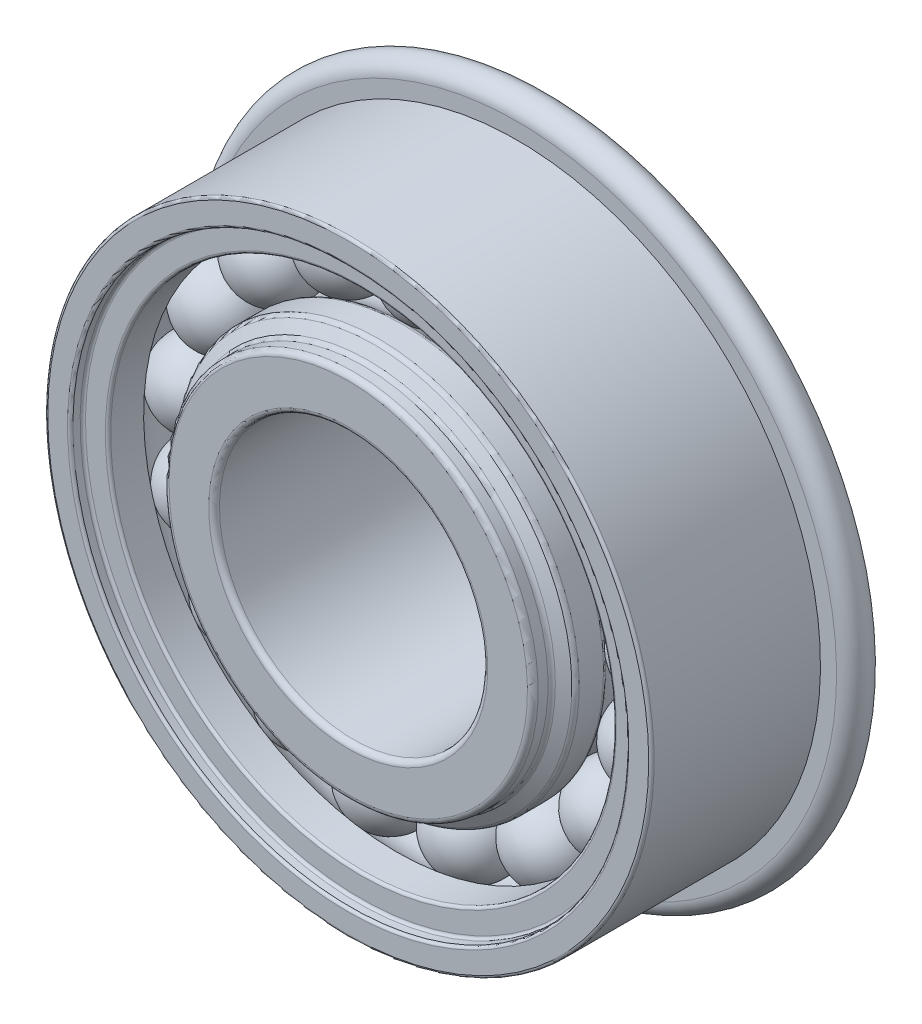
SolidWorks part; units mm, degrees
ref_plane "Front Plane" through (0, 0, 0) normal (0, 0, 1) x (1, 0, 0)
ref_plane "Top Plane" through (0, 0, 0) normal (0, 1, 0) x (1, 0, 0)
ref_plane "Right Plane" through (0, 0, 0) normal (1, 0, 0) x (0, 0, -1)
sketch "Sketch1" plane through (0, 0, 0) normal (1, 0, 0) x (0, 0, -1)
  line L0 (-5.5562, 0) -> (5.5562, 0) construction
  line L1 (3.9688, 0) -> (3.9688, 15.875)
  line L2 (3.9688, 15.875) -> (2.4448, 15.875)
  line L3 (2.4448, 15.875) -> (2.4447, 14.351)
  line L4 (2.4447, 14.351) -> (-5.5562, 14.351)
  line L5 (-5.5562, 6.35) -> (3.9688, 6.35)
  line L6 (-5.5562, 8.7376) -> (5.5563, 8.7376)
  line L7 (-1.5557, 14.351) -> (-1.5557, 10.3822) construction
  arc A0 (2.4448, 15.113) -> (3.9688, 15.113) centre (3.2068, 15.113) cw
  point P4 (0, 0)
  dimension "Inner Ring Width" = 11.1125
  dimension "Flange OD" = 31.75
  dimension "OD" = 28.702
  dimension "Width" = 9.525
  dimension "ID" = 12.7
  dimension "Inner Ring OD" = 17.4752
  dimension "Flange Thickness" = 1.524
  dimension "Ball Diameter" = 3.9688
  dimension "For Shaft Diameter" = 12.7
  dimension "For Housing ID" = 28.702
sketch "Sketch2" plane through (0, 0, 0) normal (1, 0, 0) x (0, 0, -1)
  line L0 (2.4447, 14.351) -> (-5.5562, 14.351) construction
  line L1 (2.4447, 14.351) -> (-5.5562, 14.351)
  line L2 (2.4447, 14.351) -> (2.4448, 15.113)
  line L3 (3.9688, 15.113) -> (3.9688, 11.9682)
  line L4 (3.9688, 0) -> (3.9688, 15.875) construction
  line L5 (3.9688, 11.9682) -> (0.1628, 11.9682)
  line L6 (-4.9605, 11.9682) -> (-4.9605, 13.1596)
  line L7 (-4.9605, 13.1596) -> (-5.5562, 13.1596)
  line L8 (-5.5562, 13.1596) -> (-5.5562, 14.351)
  line L9 (-1.5557, 12.9604) -> (-1.5557, 14.351) construction
  line L10 (-1.5557, 6.35) -> (-1.5557, 7.5438) construction
  line L11 (-1.5557, 7.5438) -> (-1.5557, 8.7376) construction
  line L12 (-5.5562, 8.7376) -> (5.5563, 8.7376) construction
  line L13 (-5.5562, 6.35) -> (3.9688, 6.35) construction
  line L14 (-1.5557, 12.9604) -> (-1.5557, 11.9682) construction
  line L15 (-1.5557, 11.9682) -> (-1.5557, 10.976) construction
  line L16 (-3.2743, 11.9682) -> (-4.9605, 11.9682)
  line L17 (-4.3648, 13.1596) -> (-5.5562, 13.1596) construction
  arc A0 (3.9688, 15.113) -> (2.4448, 15.113) centre (3.2068, 15.113) ccw construction
  arc A1 (3.9688, 15.113) -> (2.4448, 15.113) centre (3.2068, 15.113) ccw
  circle A2 centre (-1.5557, 10.976) radius 1.9844 construction
  arc A3 (-3.2743, 11.9682) -> (0.1628, 11.9682) centre (-1.5557, 10.976) cw
  point P10 (-1.5557, 14.351)
  point P12 (-1.5557, 8.9916)
  point P23 (-1.5557, 8.7376)
  point P24 (-1.5557, 11.9682)
  point P33 (-4.9605, 13.1596)
  dimension "D1" = 3.9688
  dimension "D2" = 0.254
revolve "Revolve1" add sketch "Sketch2" angle 360 about L0
sketch "Sketch3" plane through (0, 0, 0) normal (1, 0, 0) x (0, 0, -1)
  line L0 (-5.5562, 8.7376) -> (5.5563, 8.7376) construction
  line L1 (-5.5562, 8.7376) -> (-4.6901, 8.7376)
  line L2 (5.5563, 8.7376) -> (5.5563, 6.35)
  line L3 (5.5563, 6.35) -> (-5.5562, 6.35)
  line L4 (-5.5562, 6.35) -> (-5.5562, 8.7376)
  line L5 (2.4447, 8.7376) -> (5.5563, 8.7376)
  line L6 (-4.6901, 8.7376) -> (-4.257, 9.4877)
  line L7 (-4.257, 9.4877) -> (-2.8683, 9.4877)
  line L8 (-0.2432, 9.4877) -> (2.0117, 9.4877)
  line L9 (2.0117, 9.4877) -> (2.4447, 8.7376)
  line L10 (-1.5557, 10.976) -> (-1.5557, 9.9838) construction
  line L11 (-1.5557, 9.9838) -> (-1.5557, 8.9916) construction
  circle A2 centre (-1.5557, 10.976) radius 1.9844 construction
  arc A3 (-2.8683, 9.4877) -> (-0.2432, 9.4877) centre (-1.5557, 10.976) ccw
  point P12 (-1.5557, 9.4877)
  dimension "D1" = 60
  dimension "D2" = 60
revolve "Revolve2" add sketch "Sketch3" angle 360 about L0
sketch "Sketch5" plane through (0, 0, 0) normal (1, 0, 0) x (0, 0, -1)
  line L0 (5.5563, 6.9469) -> (5.5563, 6.35)
  line L2 (4.8866, 6.385) -> (4.4863, 6.35)
  line L8 (5.3109, 7.0126) -> (5.5563, 6.9469) construction
  line L12 (5.5563, 8.7376) -> (5.5563, 6.35) construction
  line L13 (5.5563, 6.9469) -> (5.5563, 7.5438) construction
  line L14 (5.5563, 6.35) -> (-5.5562, 6.35) construction
  line L15 (4.4863, 6.35) -> (5.5563, 6.35)
  arc A0 (5.5563, 6.9469) -> (4.8866, 6.385) centre (4.8202, 7.1441) cw
  dimension "D3" = 0.762
  dimension "D1" = 105
  dimension "D2" = 0.254
  dimension "D4" = 5
revolve "Cut-Revolve2" cut sketch "Sketch5" angle 360 about L0
sketch "Sketch6" plane through (0, 0, 0) normal (1, 0, 0) x (0, 0, -1)
  line L0 (5.3109, 7.0126) -> (5.5563, 6.9469) construction
  line L1 (5.3109, 7.0126) -> (5.5563, 6.9469)
  line L2 (5.3109, 7.0126) -> (5.5563, 7.9283) construction
  line L3 (5.5563, 8.7376) -> (5.5563, 6.35) construction
  line L4 (5.5563, 7.9283) -> (5.5563, 6.9469) construction
  line L5 (4.8645, 6.6381) -> (3.9688, 6.5597)
  line L6 (3.9688, 0) -> (3.9688, 15.875) construction
  line L7 (4.8866, 6.385) -> (4.4863, 6.35) construction
  line L8 (3.9688, 6.5597) -> (3.9688, 6.6872)
  line L9 (5.1882, 7.0455) -> (5.5563, 7.0455)
  line L10 (4.8534, 6.7646) -> (3.9688, 6.6872)
  line L11 (5.5563, 7.0455) -> (5.5563, 6.9469)
  arc A1 (5.3109, 7.0126) -> (4.8645, 6.6381) centre (4.8202, 7.1441) cw
  arc A2 (4.8534, 6.7646) -> (5.1882, 7.0455) centre (4.8202, 7.1441) ccw
  arc A3 (4.8866, 6.385) -> (5.5562, 6.9469) centre (4.8202, 7.1441) ccw construction
  dimension "D1" = 0.127
revolve "Cut-Revolve3" cut sketch "Sketch6" angle 360 about L0
fillet "Fillet4" radius 0.762 1 edges at (0, -7.0455, -5.5563)
sketch "Sketch14" plane through (0, 0, 0) normal (1, 0, 0) x (0, 0, -1)
  line L0 (3.8439, 0) -> (-3.8439, 0) construction
  line L1 (4.4863, 6.35) -> (-5.5562, 6.35)
  line L2 (-5.5562, -6.35) -> (4.4863, -6.35)
  line L3 (-5.5562, -6.35) -> (4.4863, -6.35) construction
  line L4 (4.4863, 6.35) -> (-5.5562, 6.35) construction
  line L5 (4.4863, 6.35) -> (4.7784, 6.35)
  line L6 (5.5563, 6.9469) -> (5.3109, 7.0126)
  line L7 (5.3109, -7.0126) -> (5.5563, -6.9469)
  line L8 (5.3109, -7.0126) -> (5.5563, -6.9469) construction
  line L9 (5.5563, 6.9469) -> (5.3109, 7.0126) construction
  line L10 (5.5563, 6.9469) -> (5.4336, 6.9798)
  line L11 (4.8866, -6.385) -> (4.4863, -6.35)
  line L12 (4.4863, 6.35) -> (4.8866, 6.385)
  line L13 (4.4863, 6.35) -> (4.8866, 6.385) construction
  line L14 (4.8866, -6.385) -> (4.4863, -6.35) construction
  line L15 (3.9688, -6.5597) -> (4.8645, -6.6381)
  line L16 (4.8645, 6.6381) -> (3.9688, 6.5597)
  line L17 (4.8645, 6.6381) -> (3.9688, 6.5597) construction
  line L18 (3.9688, -6.5597) -> (4.8645, -6.6381) construction
  line L19 (4.4863, 6.35) -> (4.4863, 6.477)
  line L20 (4.4863, 6.477) -> (4.6428, 6.4907)
  line L21 (4.6428, 6.4907) -> (4.6205, 6.4087) construction
  arc A0 (4.8866, 6.385) -> (5.5563, 6.9469) centre (4.8202, 7.1441) ccw
  arc A1 (5.5563, -6.9469) -> (4.8866, -6.385) centre (4.8202, -7.1441) ccw
  arc A2 (5.5563, -6.9469) -> (4.8866, -6.385) centre (4.8202, -7.1441) ccw construction
  arc A3 (4.8866, 6.385) -> (5.5563, 6.9469) centre (4.8202, 7.1441) ccw construction
  arc A4 (5.5563, 6.9469) -> (4.7784, 6.35) centre (4.7784, 7.1553) cw
  arc A5 (5.4336, 6.9798) -> (4.6428, 6.4907) centre (4.7784, 7.1553) cw
  arc A6 (4.8645, 6.6381) -> (5.3109, 7.0126) centre (4.8202, 7.1441) ccw
  arc A7 (5.3109, -7.0126) -> (4.8645, -6.6381) centre (4.8202, -7.1441) ccw
  arc A8 (5.3109, -7.0126) -> (4.8645, -6.6381) centre (4.8202, -7.1441) ccw construction
  arc A9 (4.8645, 6.6381) -> (5.3109, 7.0126) centre (4.8202, 7.1441) ccw construction
  point P4 (0, 0)
  dimension "D1" = 0.127
revolve "Revolve4" add sketch "Sketch14" angle 360 about L0
sketch "Sketch7" plane through (0, 0, 0) normal (1, 0, 0) x (0, 0, -1)
  line L0 (5.5563, 7.5438) -> (5.5563, 8.1407) construction
  line L1 (5.5563, 8.7376) -> (5.5563, 6.35) construction
  line L2 (5.5563, 8.1407) -> (5.5563, 8.7376) construction
  line L3 (5.5563, 8.1407) -> (5.5563, 8.7376)
  line L4 (5.5563, 8.7376) -> (5.3573, 8.7376)
  line L5 (-5.5562, 8.7376) -> (5.5563, 8.7376) construction
  line L6 (5.3573, 8.7376) -> (5.3573, 8.5386)
  line L7 (5.3573, 8.5386) -> (5.3573, 8.3397)
  line L8 (5.3573, 8.3397) -> (5.3573, 8.1407)
  line L9 (5.3573, 8.1407) -> (5.5563, 8.1407)
revolve "Cut-Revolve4" cut sketch "Sketch7" angle 360 about L0
sketch "Sketch11" plane through (0, 0, 0) normal (1, 0, 0) x (0, 0, -1)
  line L0 (-1.5557, 12.9604) -> (-1.5557, 8.9916)
  circle A0 centre (-1.5557, 10.976) radius 1.9844 construction
  arc A1 (-1.5557, 8.9916) -> (-1.5557, 12.9604) centre (-1.5557, 10.976) ccw
revolve "Revolve3" add sketch "Sketch11" angle 360 about L0
pattern_circular "CirPattern3" count 17 over 360 about axis through (0, 0, 5.5562) along (0, 0, -1) of bodies 111
fillet "Fillet2" radius 0.127 2 edges at (0, -13.1596, 4.9605) (0, -11.9682, 4.9605)
fillet "Fillet3" radius 0.127 2 edges at (0, -14.351, 5.5562) (0, -13.1596, 5.5562)
fillet "Fillet5" radius 0.254 9 edges at (0, -8.7376, -5.3573) (0, -8.7376, -2.4448) (0, -9.4877, 0.2432) (0, -9.4877, 2.8683) (0, -9.4877, 4.257) (0, -8.7376, 4.6901) (0, -8.7376, 5.5562) (0, -6.35, 5.5562) (0, -8.1407, -5.5563)
sketch "Sketch12" plane through (0, 0, -3.9688) normal (0, 0, -1) x (-1, 0, 0)
  line L0 (0, 11.9682) -> (0, 15.113) construction
  circle A0 centre (0, 0) radius 11.9682 construction
  circle A1 centre (0, 0) radius 11.9682
  circle A2 centre (0, 0) radius 15.113 construction
  circle A3 centre (0, 0) radius 13.5406
  point P8 (0, 13.5406)
extrude "Cut-Extrude1" cut sketch "Sketch12" against normal blind 1.143
sketch "Sketch13" plane through (0, 0, 0) normal (0, 0, 1) x (1, 0, 0)
  circle A0 centre (0, 0) radius 8.7376
  circle A1 centre (0, 0) radius 15.875
  circle A2 centre (0, 0) radius 14.351
  circle A3 centre (0, 0) radius 6.35
  point P0 (0, 8.7376)
  point P5 (0, 15.875)
  point P8 (0, 14.351)
  point P11 (0, 6.35)
equation "\"D1@Sketch2\"=\"Ball Diameter@Sketch1\""
equation "\"D1@Cut-Extrude1\"=\"Flange Thickness@Sketch1\"*.75"
